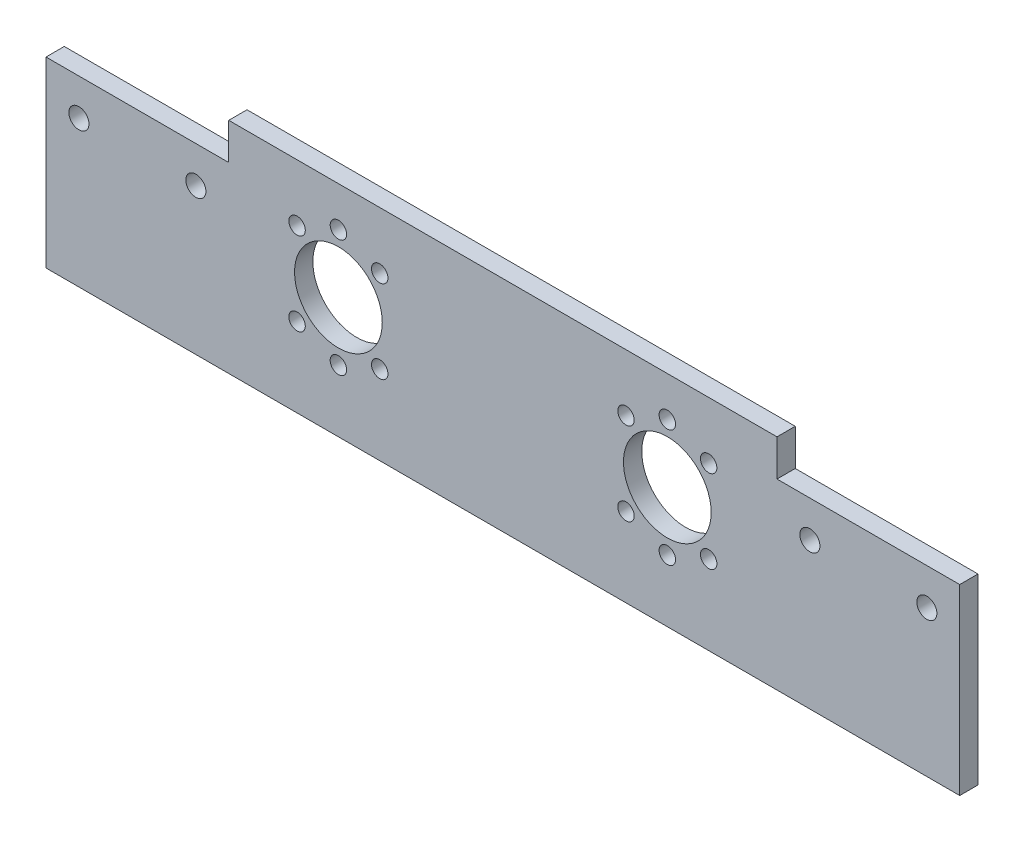
SolidWorks part; units mm, degrees
ref_plane "정면" through (0, 0, 0) normal (0, 0, 1) x (1, 0, 0)
ref_plane "윗면" through (0, 0, 0) normal (0, 1, 0) x (1, 0, 0)
ref_plane "우측면" through (0, 0, 0) normal (1, 0, 0) x (0, 0, -1)
sketch "스케치1" plane through (0, 0, 0) normal (0, 0, 1) x (1, 0, 0)
  line L1 (-145, 25) -> (145, 25)
  line L2 (-145, 25) -> (-145, -25)
  line L3 (-145, -25) -> (145, -25)
  line L4 (145, 25) -> (145, -25)
  line L5 (-145, 25) -> (145, -25) construction
  line L6 (-145, -25) -> (145, 25) construction
  point P0 (0, 0)
  dimension "D1" = 290
  dimension "D2" = 50
extrude "보스-돌출1" add sketch "스케치1" along normal blind 5
sketch "스케치3" plane through (0, 0, 5) normal (0, 0, 1) x (1, 0, 0)
  line L0 (-145, -25) -> (145, -25) construction
  line L1 (-145, 25) -> (-125, 25)
  line L2 (-145, 25) -> (-145, -25)
  line L3 (-145, -25) -> (-125, -25)
  line L4 (-125, 25) -> (-125, -25)
  dimension "D1" = 20
extrude "컷-돌출1" cut sketch "스케치3" against normal blind 10
mirror "대칭 복사1" about plane through (0, 0, 0) normal (1, 0, 0) of "컷-돌출1"
sketch "스케치4" plane through (0, 25, 0) normal (0, 1, 0) x (1, 0, 0)
  line L0 (125, 0) -> (-125, 0) construction
  line L1 (75, 0) -> (-75, 0)
  line L2 (75, 0) -> (75, -5)
  line L3 (75, -5) -> (-75, -5)
  line L4 (-75, 0) -> (-75, -5)
  line L5 (125, -5) -> (-125, -5) construction
  line L6 (-125, 0) -> (-125, -5) construction
  line L7 (125, 0) -> (125, -5) construction
  dimension "D1" = 50
  dimension "D2" = 50
extrude "보스-돌출2" add sketch "스케치4" along normal blind 10
sketch "스케치2" plane through (0, 0, 5) normal (0, 0, 1) x (1, 0, 0)
  line L2 (125, -25) -> (125, 25) construction
  line L3 (-125, -25) -> (125, -25) construction
  line L4 (9.7684, 8.045) -> (97.0125, 8.045) construction
  line L5 (44.999, 47.2348) -> (44.999, -36.4598) construction
  line L6 (0, -2.75) -> (0, 2.75) construction
  line L7 (-75, 35) -> (75, 35) construction
  circle A2 centre (56.308, -3.31) radius 2.25
  circle A3 centre (33.69, -3.31) radius 2.25
  circle A4 centre (44.999, -8) radius 2.25
  circle A5 centre (56.308, 19.4) radius 2.25
  circle A6 centre (44.999, 24.09) radius 2.25
  circle A7 centre (33.69, 19.4) radius 2.25
  circle A8 centre (-33.69, 19.4) radius 2.25
  circle A9 centre (-44.999, 24.09) radius 2.25
  circle A10 centre (-56.308, 19.4) radius 2.25
  circle A11 centre (-44.999, -8) radius 2.25
  circle A12 centre (-33.69, -3.31) radius 2.25
  circle A13 centre (-56.308, -3.31) radius 2.25
  circle A16 centre (44.999, 8.045) radius 12
  dimension "D4" = 68.692
  dimension "D5" = 15.6
  dimension "D7" = 4.5
  dimension "D11" = 4.5
  dimension "D2" = 24
  dimension "D3" = 91.31
  dimension "D8" = 21.69
  dimension "D10" = 17
extrude "컷-돌출2" cut sketch "스케치2" against normal blind 2.5
extrude "컷-돌출3" cut sketch "스케치2<2>" against normal through all contours A10 | A9 | A8 | A13 | A11 | A12 | A2 | A5 | A6 | A7 | A3 | A4 region at (56.308, -3.31, 5) region at (56.308, 19.4, 5) region at (44.999, 24.09, 5) region at (33.69, 19.4, 5) region at (-33.69, 19.4, 5) region at (-44.999, 24.09, 5) region at (-56.308, 19.4, 5) region at (-44.999, -8, 5) region at (-33.69, -3.31, 5) region at (-56.308, -3.31, 5)
sketch "스케치2<2>" plane through (0, 0, 5) normal (0, 0, 1) x (1, 0, 0) same geometry as "스케치2"
sketch "스케치5" plane through (0, 0, 5) normal (0, 0, 1) x (1, 0, 0)
  line L0 (-75, 25) -> (-125, 25) construction
  line L1 (-125, -25) -> (-125, 25) construction
  line L2 (0, -2.75) -> (0, 2.75) construction
  circle A0 centre (-84, 15) radius 2.75
  circle A1 centre (-116, 15) radius 2.75
  circle A2 centre (116, 15) radius 2.75
  circle A3 centre (84, 15) radius 2.75
  dimension "D3" = 5.5
  dimension "D4" = 5.5
  dimension "D5" = 9
  dimension "D1" = 10
  dimension "D2" = 10
  dimension "D6" = 41
extrude "컷-돌출4" cut sketch "스케치5" against normal through all
extrude "컷-돌출5" cut sketch "스케치2<3>" against normal blind 10 contours A16 region at (44.999, 8.045, 5)
sketch "스케치2<3>" plane through (0, 0, 5) normal (0, 0, 1) x (1, 0, 0) same geometry as "스케치2"
ref_plane "평면1" through (0, 0, 0) normal (1, 0, 0) x (0, 0, -1)
mirror "대칭 복사2" about plane through (0, 0, 0) normal (1, 0, 0) of "컷-돌출5"
